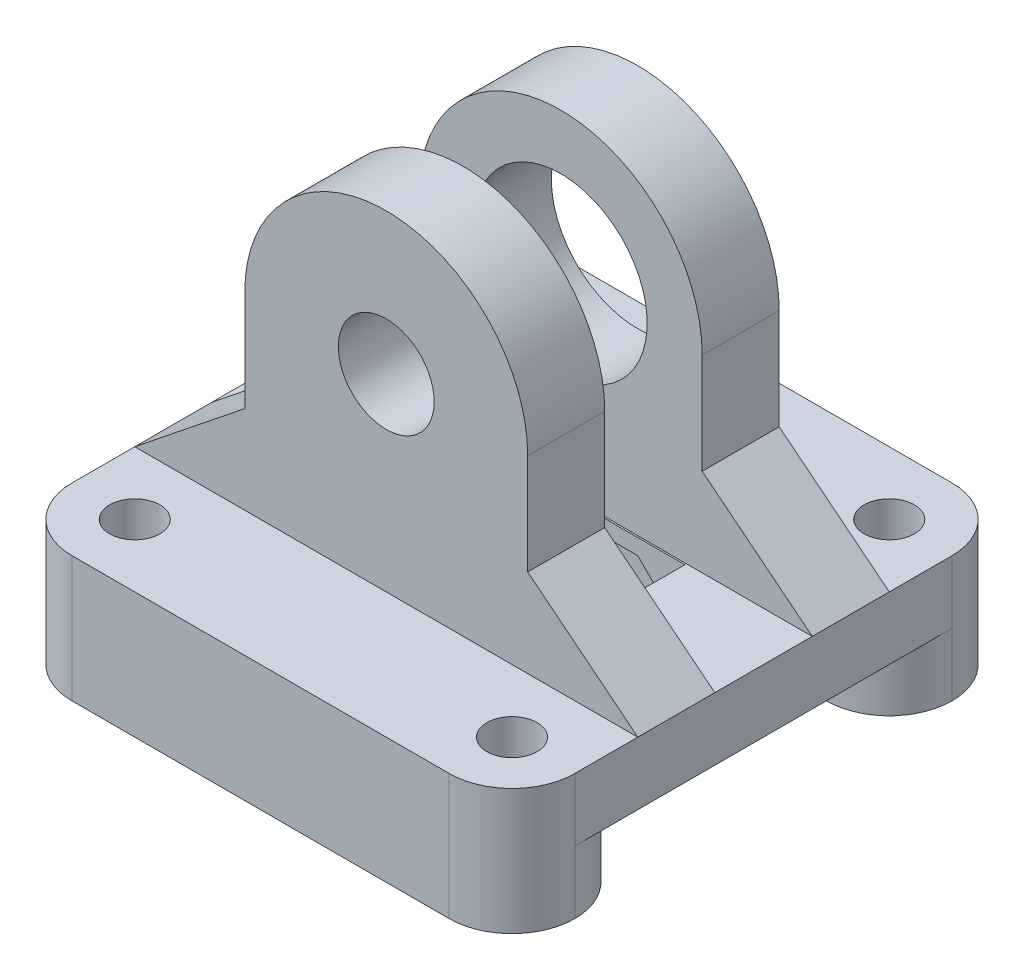
SolidWorks part; units mm, degrees
ref_plane "Front Plane" through (0, 0, 0) normal (0, 0, 1) x (1, 0, 0)
ref_plane "Top Plane" through (0, 0, 0) normal (0, 1, 0) x (1, 0, 0)
ref_plane "Right Plane" through (0, 0, 0) normal (1, 0, 0) x (0, 0, -1)
sketch "Sketch1" plane through (0, 0, 0) normal (0, 1, 0) x (1, 0, 0)
  line L0 (0, 0) -> (0, 12) construction
  line L1 (0, 12) -> (8, 12) construction
  line L2 (0, 0) -> (22.796, 0) construction
  line L3 (-12, 16) -> (12, 16)
  line L4 (8, 8) -> (-8, 8)
  line L5 (8, -8) -> (-8, -8)
  line L6 (-12, -16) -> (12, -16)
  line L7 (-16, -12) -> (-16, 12)
  line L8 (16, 12) -> (16, -12)
  line L9 (8, -8) -> (8, 8)
  line L10 (-8, 8) -> (-8, -8)
  line L11 (10.4, 12) -> (12, 12) construction
  circle A0 centre (12, 12) radius 1.6
  circle A1 centre (-12, 12) radius 1.6
  arc A4 (-12, 16) -> (-16, 12) centre (-12, 12) ccw
  arc A5 (16, 12) -> (12, 16) centre (12, 12) ccw
  circle A6 centre (12, -12) radius 1.6
  arc A7 (16, -12) -> (12, -16) centre (12, -12) cw
  arc A8 (-12, -16) -> (-16, -12) centre (-12, -12) cw
  circle A9 centre (-12, -12) radius 1.6
  dimension "D1" = 12
  dimension "D2" = 12
extrude "Boss-Extrude1" add sketch "Sketch1" along normal blind 8
sketch "Sketch2" plane through (16, 0, 0) normal (1, 0, 0) x (0, 0, -1)
  line L0 (-12, 0) -> (-8, 0)
  line L1 (-12, 0) -> (12, 0) construction
  line L2 (12, 0) -> (8, 0)
  line L3 (8, 0) -> (8, 4)
  line L4 (8, 4) -> (-8, 4)
  line L5 (-8, 4) -> (-8, 0)
  line L6 (-8, 0) -> (8, 0)
  line M1 (-12, 0) -> (12, 0)
extrude "Cut-Extrude1" cut sketch "Sketch2" against normal blind 40 contours L4 L5 L3 M1 region at (16, 2, 0)
fillet "Fillet1" radius 4 4 edges at (-16, 2, -8) (16, 2, -8) (-16, 2, 8) (16, 2, 8)
sketch "Sketch3" plane through (0, 8, 0) normal (0, 1, 0) x (1, 0, 0)
  line L0 (-16, 8) -> (16, 8)
  line L1 (-16, 12) -> (-16, -12) construction
  line L2 (16, -12) -> (16, 12) construction
  line L3 (-16, -8) -> (16, -8)
  line L4 (16, -8) -> (16, -3)
  line L5 (16, -3) -> (-16, -3)
  line L6 (-16, -3) -> (-16, -8)
  line L7 (-16, 8) -> (-16, 3)
  line L8 (-16, 3) -> (16, 3)
  line L9 (16, 3) -> (16, 8)
extrude "Boss-Extrude5" add sketch "Sketch3" along normal blind 8 and the other way blind 1
chamfer "Chamfer1" distance 3 angle 45 4 edges at (8, 7, 5.5) (8, 7, -5.5) (-8, 7, -5.5) (-8, 7, 5.5)
chamfer "Chamfer2" distance 8 distance2 10 4 edges at (16, 16, -5.5) (-16, 16, -5.5) (16, 16, 5.5) (-16, 16, 5.5) first distance on face at (16, 10, 0) first distance on face at (-16, 10, 0)
sketch "Sketch5" plane through (0, 16, 0) normal (0, 1, 0) x (1, 0, 0)
  line L0 (-6, 8) -> (6, 8)
  line L1 (6, 8) -> (6, 3)
  line L2 (6, 3) -> (-6, 3)
  line L3 (-6, 3) -> (-6, 8)
  line L4 (-6, -3) -> (6, -3)
  line L5 (6, -3) -> (6, -8)
  line L6 (6, -8) -> (-6, -8)
  line L7 (-6, -8) -> (-6, -3)
extrude "Boss-Extrude7" add sketch "Sketch5" along normal blind 8
fillet "Fillet2" radius 4 4 edges at (-6, 24, -5.5) (6, 24, -5.5) (6, 24, 5.5) (-6, 24, 5.5)
sketch "Sketch6" plane through (0, 0, 8) normal (0, 0, 1) x (1, 0, 0)
  circle A0 centre (0, 20) radius 1.6
extrude "Cut-Extrude2" cut sketch "Sketch6" against normal blind 20
sketch "Sketch7" plane through (0, 0, 8) normal (0, 0, 1) x (1, 0, 0)
  circle A0 centre (0, 20) radius 3.05
extrude "Cut-Extrude3" cut sketch "Sketch7" against normal blind 9
sketch "Sketch8" plane through (0, 0, 8) normal (0, 0, 1) x (1, 0, 0)
  line L0 (-9, 20) -> (-9, 11)
  line L1 (-9, 11) -> (0, 11)
  line L2 (9, 20) -> (9, 11)
  line L3 (9, 11) -> (0, 11)
  arc A0 (9, 20) -> (-9, 20) centre (0, 20) ccw
  circle A1 centre (0, 20) radius 3.05
extrude "Boss-Extrude8" add sketch "Sketch8" against normal up to surface (5 mm away) up to face at (-3.05, 20, 3)
sketch "Sketch9" plane through (0, 0, -8) normal (0, 0, -1) x (-1, 0, 0)
  line L0 (-9, 20) -> (-9, 11)
  line L1 (9, 20) -> (9, 11)
  line L2 (9, 11) -> (-9, 11)
  circle A1 centre (0, 20) radius 1.6
  arc A2 (9, 20) -> (-9, 20) centre (0, 20) ccw
extrude "Boss-Extrude9" add sketch "Sketch9" against normal up to surface (5 mm away) up to face at (1.6, 20, -3)
sketch "Sketch10" plane through (0, 0, -8) normal (0, 0, -1) x (-1, 0, 0)
  circle A0 centre (0, 20) radius 5.5
extrude "Cut-Extrude4" cut sketch "Sketch10" against normal blind 9
sketch "Sketch11" plane through (0, 8, 0) normal (0, 1, 0) x (1, 0, 0)
  line L0 (0, 0) -> (0, 3.1)
  line L1 (0, 3.1) -> (23.9616, 3.1)
  line L2 (23.9616, 3.1) -> (23.9616, -3.1)
  line L3 (23.9616, 0) -> (-29.3911, 0)
  line L4 (0, 3.1) -> (-29.3911, 3.1)
  line L5 (-29.3911, 3.1) -> (-29.3911, -3.1)
  line L6 (0, -3.1) -> (-29.3911, -3.1)
  line L7 (0, -3.1) -> (23.9616, -3.1)
  line M7 (-8, -3) -> (-8, 3)
  line M8 (-8, 3) -> (-16, 3)
  line M9 (-16, 3) -> (-16, -3)
extrude "Cut-Extrude5" cut sketch "Sketch11" along normal blind 37 contours L3 L2 L1 L0 | L4 L5 L3 L0 M9 M8 M7 | L3 M7 M8 M9 | L4 L5 L6 L7 L2 L1 region at (-4, 8, -0.2955) region at (11.9808, 8, -1.55) region at (-12, 8, -1.5)
